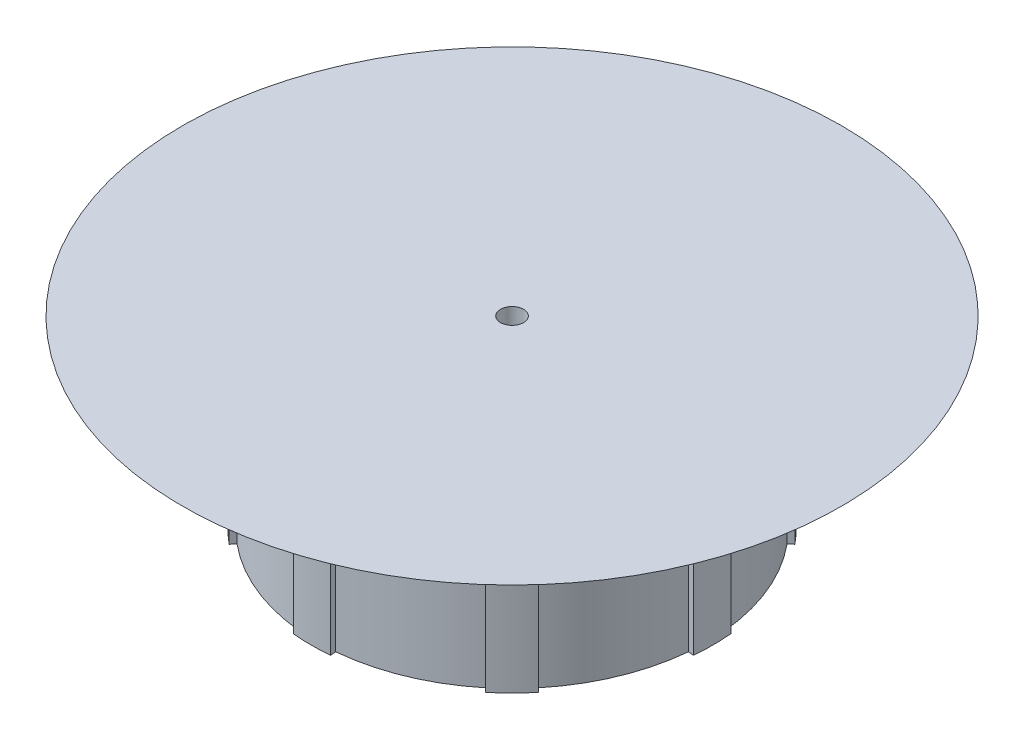
SolidWorks part; units mm, degrees
ref_plane "Front Plane" through (0, 0, 0) normal (0, 0, 1) x (1, 0, 0)
ref_plane "Top Plane" through (0, 0, 0) normal (0, 1, 0) x (1, 0, 0)
ref_plane "Right Plane" through (0, 0, 0) normal (1, 0, 0) x (0, 0, -1)
sketch "Sketch1" plane through (0, 0, 0) normal (0, 0, 1) x (1, 0, 0)
  line L0 (0, 0) -> (0, 23.3158) construction
  line L1 (23.2283, 15.24) -> (38.1, 21.336)
  line L2 (0, 0) -> (23.2283, 0)
  line L3 (0, 0) -> (0, 15.24)
  line L4 (0, 15.24) -> (23.2283, 15.24)
  line L5 (23.2283, 0) -> (23.2283, 15.24)
  line L6 (38.1, 21.336) -> (0, 21.336)
  point P6 (26.9972, 15.24)
  dimension "D1" = 76.2
  dimension "D2" = 6.096
  dimension "D3" = 15.24
  dimension "D4" = 46.4566
revolve "Revolve1" add sketch "Sketch1" angle 360 about L0 region at (11.6142, 7.62, 0) region at (15.6326, 18.5344, 0)
sketch "Sketch2" plane through (0, 0, 0) normal (0, -1, 0) x (1, 0, 0)
  line L0 (0, 0) -> (0, 23.2283) construction
  line L1 (0, 0) -> (-2.159, 23.1277)
  line L2 (0, 0) -> (2.159, 23.1277)
  line L3 (0, 0) -> (14.8271, 17.8804)
  line L4 (0, 0) -> (17.8804, 14.8271)
  line L5 (0, 0) -> (23.1277, 2.159)
  line L6 (0, 0) -> (23.1277, -2.159)
  line L7 (0, 0) -> (17.8804, -14.8271)
  line L8 (0, 0) -> (14.8271, -17.8804)
  line L9 (0, 0) -> (2.159, -23.1277)
  line L10 (0, 0) -> (-2.159, -23.1277)
  line L11 (0, 0) -> (-14.8271, -17.8804)
  line L12 (0, 0) -> (-17.8804, -14.8271)
  line L13 (0, 0) -> (-23.1277, -2.159)
  line L14 (0, 0) -> (-23.1277, 2.159)
  line L15 (0, 0) -> (-17.8804, 14.8271)
  line L16 (0, 0) -> (-14.8271, 17.8804)
  circle A0 centre (0, 0) radius 22.5806
  circle A2 centre (0, 0) radius 23.2283 construction
  circle A3 centre (0, 0) radius 23.2283 construction
  circle A4 centre (0, 0) radius 23.2283
  circle A6 centre (0, 0) radius 23.2283
  point P29 (0, 0)
  circle M5 centre (0, 0) radius 23.2283
  dimension "D2" = 0.6477
  dimension "D1" = 4.318
  dimension "D3" = 0
  dimension "D4" = 8
extrude "Cut-Extrude1" cut sketch "Sketch2" against normal blind 15.24 contours A0 L3 L2 M5 | A0 L1 L16 M5 | A0 L15 L14 M5 | A0 L13 L12 M5 | A0 L11 L10 M5 | A0 L9 L8 M5 | A0 L7 L6 M5 | A0 L5 L4 M5 region at (-8.6947, 0, 20.9908) region at (2.2679, 0, 22.7923) region at (17.7203, 0, 14.5129) region at (22.7923, 0, -2.2679) region at (14.5129, 0, -17.7203) region at (-2.2679, 0, -22.7923) region at (-17.7203, 0, -14.5129) region at (-22.7923, 0, 2.2679)
sketch "Sketch3" plane through (0, 21.336, 0) normal (0, 1, 0) x (1, 0, 0)
  circle A0 centre (0, 0) radius 1.335
  dimension "D1" = 2.67
extrude "Cut-Extrude2" cut sketch "Sketch3" against normal blind 15.24
